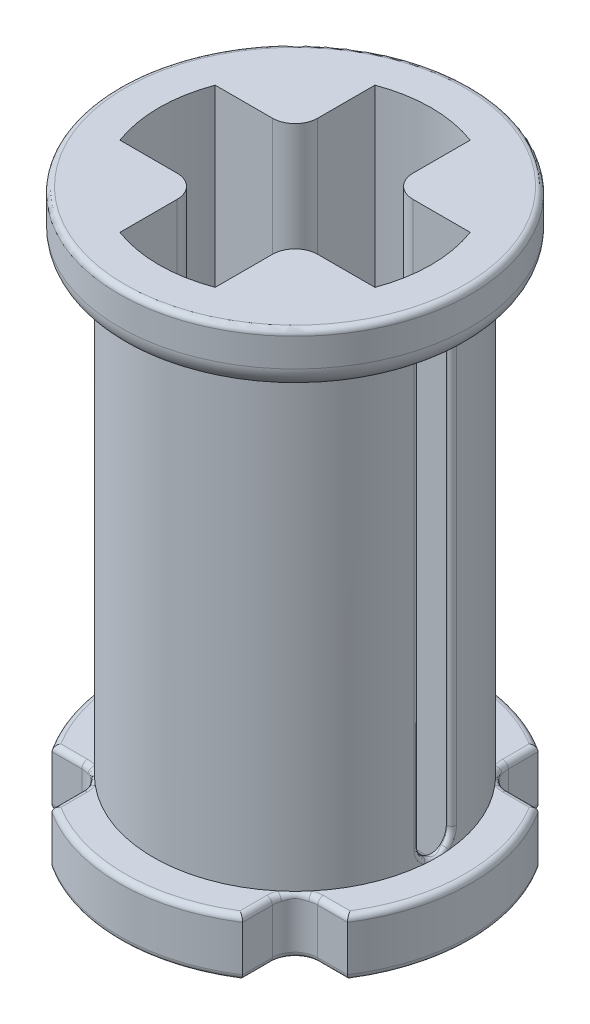
SolidWorks part; units mm, degrees
ref_plane "Front Plane" through (0, 0, 0) normal (0, 0, 1) x (1, 0, 0)
ref_plane "Top Plane" through (0, 0, 0) normal (0, 1, 0) x (1, 0, 0)
ref_plane "Right Plane" through (0, 0, 0) normal (1, 0, 0) x (0, 0, -1)
sketch "Sketch8" plane through (0, 0, 0) normal (0, 1, 0) x (1, 0, 0)
  circle A0 centre (0, 0) radius 3.1
  dimension "D1" = 6.2
extrude "Boss-Extrude4" add sketch "Sketch8" along normal blind 10
sketch "Sketch9" plane through (0, 0, 0) normal (0, 1, 0) x (1, 0, 0)
  line L0 (1.24, 0.84) -> (2.2482, 0.84)
  line L2 (-0.84, 2.2482) -> (-0.84, 1.24)
  line L4 (0.84, 2.2482) -> (0.84, 1.24)
  line L5 (-0.84, 2.2482) -> (0.84, -2.2482) construction
  line L6 (-0.84, -2.2482) -> (0.84, 2.2482) construction
  line L7 (-2.2482, 0.84) -> (-1.24, 0.84)
  line L9 (-2.2482, -0.84) -> (-1.24, -0.84)
  line L11 (-2.2482, 0.84) -> (2.2482, -0.84) construction
  line L12 (-2.2482, -0.84) -> (2.2482, 0.84) construction
  line L13 (1.24, -0.84) -> (2.2482, -0.84)
  line L14 (-0.84, -1.24) -> (-0.84, -2.2482)
  line L15 (0.84, -1.24) -> (0.84, -2.2482)
  circle A0 centre (0, 0) radius 2.4
  arc A1 (1.24, -0.84) -> (0.84, -1.24) centre (1.24, -1.24) ccw
  arc A2 (-1.24, -0.84) -> (-0.84, -1.24) centre (-1.24, -1.24) cw
  arc A3 (1.24, 0.84) -> (0.84, 1.24) centre (1.24, 1.24) cw
  arc A4 (-1.24, 0.84) -> (-0.84, 1.24) centre (-1.24, 1.24) ccw
  point P17 (0.84, -0.84)
  point P20 (-0.84, -0.84)
  dimension "D1" = 4.8
  dimension "D4" = 0.4
  dimension "D2" = 1.68
  dimension "D3" = 1.68
extrude "Cut-Extrude1" cut sketch "Sketch9" along normal blind 10 contours A4 L7 A0 L9 A2 L14 L15 A1 L13 L0 A3 L4 L2 region at (0, 0, 0)
sketch "Sketch10" plane through (0, 0, 0) normal (0, -1, 0) x (1, 0, 0)
  line L0 (-2.08, -1.68) -> (-2.6053, -1.68)
  line L2 (1.68, -2.6053) -> (1.68, -2.08)
  line L4 (-1.68, -2.6053) -> (-1.68, -2.08)
  line L5 (1.68, -2.6053) -> (1.0833, -1.68) construction
  line L6 (1.68, 2.6053) -> (-1.68, -2.6053) construction
  line L7 (2.6053, -1.68) -> (2.08, -1.68)
  line L9 (2.6053, 1.68) -> (2.08, 1.68)
  line L11 (2.6053, -1.68) -> (-2.6053, 1.68) construction
  line L12 (2.6053, 1.68) -> (-2.6053, -1.68) construction
  line L13 (0, 0) -> (-1.68, 2.6053) construction
  line L14 (1.68, 2.08) -> (1.68, 2.6053)
  line L15 (-2.08, 1.68) -> (-2.6053, 1.68)
  line L16 (-1.68, 2.08) -> (-1.68, 2.6053)
  circle A0 centre (0, 0) radius 3.1 construction
  arc A1 (1.68, 2.08) -> (2.08, 1.68) centre (2.08, 2.08) ccw
  arc A2 (-2.08, 1.68) -> (-1.68, 2.08) centre (-2.08, 2.08) ccw
  arc A3 (-2.08, -1.68) -> (-1.68, -2.08) centre (-2.08, -2.08) cw
  arc A4 (2.08, -1.68) -> (1.68, -2.08) centre (2.08, -2.08) ccw
  circle A5 centre (0, 0) radius 3.1
  point P0 (0, 0)
  point P8 (0, 0)
  point P23 (-1.68, 1.68)
  circle M19 centre (0, 0) radius 3.1
  dimension "D3" = 0.4
  dimension "D1" = 3.36
  dimension "D2" = 3.36
extrude "Cut-Extrude2" cut sketch "Sketch10" against normal blind 9 contours L7 A4 L2 M19 | A3 L0 L4 M19 | L15 A2 L16 M19 | L14 A1 L9 M19 region at (-2.0283, 0, -2.0283) region at (-2.0283, 0, 2.0283) region at (2.0283, 0, -2.0283) region at (2.0283, 0, 2.0283)
ref_plane "Plane1" through (0, 5, 0) normal (0, 1, 0) x (1, 0, 0)
sketch "Sketch13" plane through (0, 5, 0) normal (0, 1, 0) x (1, 0, 0)
  circle A0 centre (0, 0) radius 2.5
  circle A1 centre (0, 0) radius 3.1
  dimension "D1" = 5
  dimension "D2" = 6.2
extrude "Cut-Extrude4" cut sketch "Sketch13" against normal mid plane 8
fillet "Fillet1" radius 0.1 32 edges at (-2.3427, 0, -1.68) (-1.7972, 0, -1.7972) (-1.68, 0, 2.3427) (-1.7972, 0, 1.7972) (1.68, 0, 2.3427) (1.7972, 0, 1.7972) (-3.1, 0, 0) (-1.68, 0, -2.3427) (-2.3427, 0, 1.68) (2.3427, 0, 1.68) (0, 0, 3.1) (3.1, 0, 0) (0, 0, -3.1) (2.3427, 0, -1.68) (1.7972, 0, -1.7972) (1.68, 0, -2.3427) (0, 0, -2.4) (0.84, 0, -1.7441) (0.9572, 0, -0.9572) (1.7441, 0, -0.84) (2.4, 0, 0) (1.7441, 0, 0.84) (0.9572, 0, 0.9572) (0.84, 0, 1.7441) (0, 0, 2.4) (-0.84, 0, 1.7441) (-0.9572, 0, 0.9572) (-1.7441, 0, 0.84) (-2.4, 0, 0) (-1.7441, 0, -0.84) (-0.9572, 0, -0.9572) (-0.84, 0, -1.7441)
fillet "Fillet2" radius 0.4 1 edges at (0, 9, -3.1)
sketch "Sketch15" plane through (0, 0, 0) normal (1, 0, 0) x (0, 0, -1)
  line L0 (0, 8.7059) -> (0, 1.2941) construction
  line L5 (3.41, 5) -> (-3.41, 5) construction
  line L6 (0.2843, 8.7059) -> (0.2843, 1.2941)
  line L7 (-0.2843, 8.7059) -> (-0.2843, 1.2941)
  arc A2 (0.2843, 8.7059) -> (-0.2843, 8.7059) centre (0, 8.7059) ccw
  arc A3 (-0.2843, 1.2941) -> (0.2843, 1.2941) centre (0, 1.2941) ccw
  point P4 (0, 5)
extrude "Cut-Extrude5" cut sketch "Sketch15" along normal blind 3 and the other way blind 3
fillet "Fillet3" radius 0.1 1 edges at (0, 10, 3.1)
fillet "Fillet4" radius 0.1 16 edges at (1.68, 1, 2.3427) (1.7972, 1, 1.7972) (2.3427, 1, -1.68) (1.7972, 1, -1.7972) (-1.68, 1, 2.3427) (-1.7972, 1, 1.7972) (-1.68, 1, -2.3427) (-1.7972, 1, -1.7972) (2.3427, 1, 1.68) (1.68, 1, -2.3427) (3.1, 1, 0) (-2.3427, 1, 1.68) (0, 1, 3.1) (0, 1, -3.1) (-2.3427, 1, -1.68) (-3.1, 1, 0)
fillet "Fillet5" radius 0.08 8 edges at (-2.4998, 8.9883, -0.032) (-2.4838, 5, 0.2843) (-2.4998, 1.0117, 0.032) (2.4998, 1.0117, -0.032) (2.4838, 5, 0.2843) (2.4998, 8.9883, 0.032) (-2.4838, 5, -0.2843) (2.4838, 5, -0.2843)
